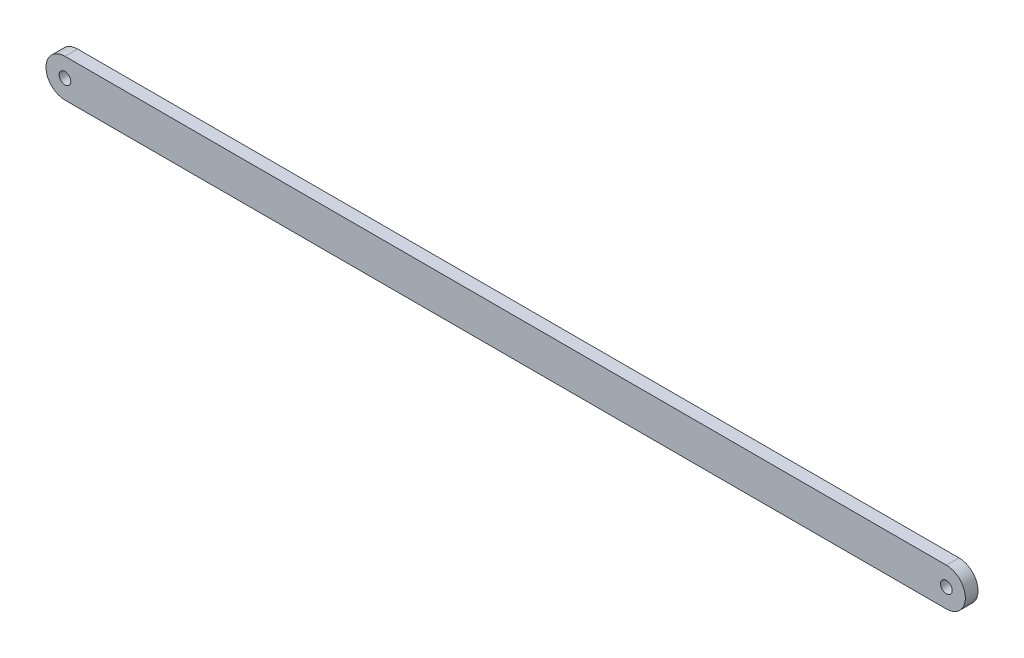
SolidWorks part; units mm, degrees
ref_plane "前视基准面" through (0, 0, 0) normal (0, 0, 1) x (1, 0, 0)
ref_plane "上视基准面" through (0, 0, 0) normal (0, 1, 0) x (1, 0, 0)
ref_plane "右视基准面" through (0, 0, 0) normal (1, 0, 0) x (0, 0, -1)
other "Configuration Table"
sketch "草图1" plane through (0, 0, 0) normal (0, 0, 1) x (1, 0, 0)
  line L1 (-174.2494, 7.5) -> (174.2494, 7.5)
  line L3 (-174.2494, -7.5) -> (174.2494, -7.5)
  line L5 (-174.2494, 7.5) -> (174.2494, -7.5) construction
  line L6 (-174.2494, -7.5) -> (174.2494, 7.5) construction
  arc A0 (-174.2494, 7.5) -> (-174.2494, -7.5) centre (-174.2494, 0) ccw
  arc A1 (174.2494, 7.5) -> (174.2494, -7.5) centre (174.2494, 0) cw
  circle A2 centre (-174.2494, 0) radius 2.3
  circle A3 centre (174.2494, 0) radius 2.3
  point P0 (0, 0)
  dimension "D1" = 4.6
  dimension "D2" = 4.6
  dimension "D3" = 348.4988
  dimension "D4" = 15
extrude "凸台-拉伸1" add sketch "草图1" along normal blind 5
equation "\"fi\"=4.6"
equation "\"D1@草图1\"=\"fi\""
equation "\"D2@草图1\"=\"fi\""
equation "\"b0\"=75.6"
equation "\"D3@草图1\"=\"b5\""
equation "\"width\"=15"
equation "\"D4@草图1\"=\"width\""
equation "\"depth\"=5"
equation "\"D1@凸台-拉伸1\"=\"depth\""
equation "\"b1\"= \"b0\" * 3 / 2"
equation "\"b2\"= \"b0\" * 6 / 2"
equation "\"b3\"= \"b0\" * 4 / 2"
equation "\"b4\"= \"b0\" * 7 / 2"
equation "\"angle\"= 90度"
equation "\"b5\"=(\"b2\"^2+\"b4\"^2)^0.5"
